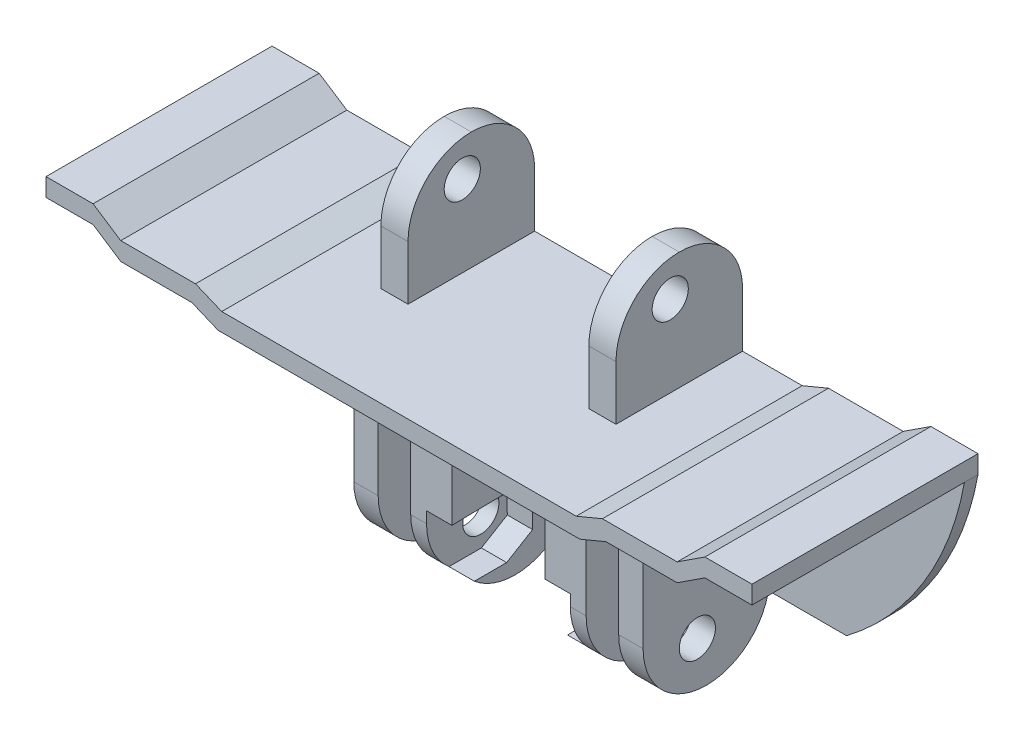
SolidWorks part; units mm, degrees
ref_plane "Front Plane" through (0, 0, 0) normal (0, 0, 1) x (1, 0, 0)
ref_plane "Top Plane" through (0, 0, 0) normal (0, 1, 0) x (1, 0, 0)
ref_plane "Right Plane" through (0, 0, 0) normal (1, 0, 0) x (0, 0, -1)
sketch "Sketch2" plane through (0, 0, 0) normal (0, 0, 1) x (1, 0, 0)
  line L0 (-5, 6) -> (-10, 6)
  line L1 (-5, 6) -> (5, 6) construction
  line L2 (-5, 6) -> (-5, -19) construction
  line L4 (5, 6) -> (5, -19) construction
  line L7 (-10, 6) -> (-10, -19)
  line L8 (-10, -19) -> (-5, -19)
  line L9 (-5, -19) -> (-5, 6)
  line L10 (0, 6) -> (0, -6) construction
  line L11 (10, -19) -> (5, -19)
  line L12 (10, 6) -> (10, -19)
  line L13 (5, 6) -> (10, 6)
  line L14 (5, -19) -> (5, 6)
  point P0 (0, 0)
  point P11 (0, 0)
  point P16 (0, 6)
  dimension "D1" = 25
  dimension "D2" = 10
  dimension "D3" = 5
extrude "Boss-Extrude1" add sketch "Sketch2" along normal blind 14
sketch "Sketch4" plane through (0, 0, 0) normal (0, 0, 1) x (1, 0, 0)
  line L0 (0, 0) -> (0, 50000) construction
  line L1 (-6.1796, 6) -> (49993.8204, 6) construction
  line L2 (-10, 6) -> (-20, 6)
  line L3 (10, 6) -> (20, 6)
  line L4 (-20, 6) -> (-22.9016, 7.2064)
  line L5 (-22.9016, 7.2064) -> (-26, 7.2064)
  line L6 (-10, 8) -> (-19.6008, 8)
  line L7 (-19.6008, 8) -> (-22.5024, 9.2064)
  line L8 (-22.5024, 9.2064) -> (-26, 9.2064)
  line L9 (-26, 9.2064) -> (-26, 7.2064)
  line L10 (-10, 6) -> (10, 6)
  line L11 (-10, 8) -> (10, 8)
  line L12 (10, 8) -> (19.6008, 8)
  line L13 (19.6008, 8) -> (22.5024, 9.2064)
  line L14 (20, 6) -> (22.9016, 7.2064)
  line L15 (22.9016, 7.2064) -> (26, 7.2064)
  line L17 (22.5024, 9.2064) -> (26, 9.2064)
  line L18 (-26, 7.2064) -> (-30.766, 7.2064)
  line L19 (-30.766, 7.2064) -> (-33.8312, 9.2064)
  line L20 (-33.8312, 9.2064) -> (-39.0379, 9.2064)
  line L21 (-39.0379, 9.2064) -> (-39.0379, 11.2064)
  line L22 (-39.0379, 11.2064) -> (-33.8312, 11.2064)
  line L23 (-26, 9.2064) -> (-30.766, 9.2064)
  line L24 (-30.766, 9.2064) -> (-33.8312, 11.2064)
  line L25 (26, 7.2064) -> (30.766, 7.2064)
  line L26 (26, 9.2064) -> (30.766, 9.2064)
  line L27 (30.766, 9.2064) -> (33.8312, 11.2064)
  line L28 (30.766, 7.2064) -> (33.8312, 9.2064)
  line L29 (33.8312, 9.2064) -> (39.0379, 9.2064)
  line L30 (39.0379, 9.2064) -> (39.0379, 11.2064)
  line L31 (39.0379, 11.2064) -> (33.8312, 11.2064)
  line L32 (26, 7.2064) -> (26, 9.2064)
  point P19 (0, 6)
  point P20 (0, 8)
  dimension "D1" = 10
  dimension "D2" = 2
extrude "Boss-Extrude3" add sketch "Sketch4" along normal blind 25 contours L23 L24 L22 L21 L20 L19 L18 L9 | L15 L32 L17 L13 L12 L11 L6 L7 L8 L9 L5 L4 L2 L10 L3 L14 | L32 L25 L28 L29 L30 L31 L27 L26 region at (0, 7.2239, 0) region at (-32.5189, 9.2402, 0) region at (32.5189, 9.2402, 0)
sketch "Sketch9" plane through (0, 0, 14) normal (0, 0, 1) x (1, 0, 0)
  line L0 (-10, -19) -> (-5, -19) construction
  line L1 (-5, 6) -> (-7.5, 6)
  line L2 (-5, 6) -> (-5, -19)
  line L3 (-5, -19) -> (-7.5, -19)
  line L4 (-7.5, 6) -> (-7.5, -19)
  line L5 (0, 7.972) -> (0, -7.972) construction
  line L6 (5, -19) -> (7.5, -19)
  line L7 (7.5, 6) -> (7.5, -19)
  line L8 (5, 6) -> (7.5, 6)
  line L9 (5, 6) -> (5, -19)
  point P11 (0, 0)
  dimension "D1" = 2.5
extrude "Cut-Extrude1" [suppressed] cut sketch "Sketch9" against normal blind 10
sketch "Sketch5" plane through (0, 0, 0) normal (0, 0, 1) x (1, 0, 0)
  line L0 (-10, 4.6) -> (-10, 50004.6) construction
  line L1 (0, 0) -> (0, 50000) construction
  line L2 (-10, 8) -> (-10, 21)
  line L3 (-19.6008, 8) -> (19.6008, 8) construction
  line L4 (-10, 21) -> (-13, 21)
  line L5 (-13, 21) -> (-13, 8)
  line L6 (-13, 8) -> (-10, 8)
  line L7 (13, 8) -> (10, 8)
  line L8 (13, 21) -> (13, 8)
  line L9 (10, 21) -> (13, 21)
  line L10 (10, 8) -> (10, 21)
  dimension "D1" = 3
  dimension "D2" = 13
extrude "Boss-Extrude4" add sketch "Sketch5" along normal blind 14
sketch "Sketch7" plane through (0, 0, 0) normal (0, 0, 1) x (1, 0, 0)
  line L0 (-13, 5.6) -> (-13, -49994.4) construction
  line L1 (-19.6008, 5.6) -> (-19.6008, -49994.4) construction
  line L2 (-10.0004, -19) -> (49989.9996, -19) construction
  line L3 (-15.0004, 6) -> (-50015.0004, 6) construction
  line L4 (-16, 6) -> (-16, -19)
  line L5 (-16, -19) -> (-13, -19)
  line L6 (-13, -19) -> (-13, 6)
  line L7 (-13, 6) -> (-16, 6)
  line L8 (0, 0) -> (0, -50000) construction
  line L13 (0, -13.75) -> (0, 13.75) construction
  line L14 (13, -19) -> (13, 6)
  line L15 (16, -19) -> (13, -19)
  line L16 (16, 6) -> (16, -19)
  line L17 (13, 6) -> (16, 6)
  dimension "D1" = 3
extrude "Boss-Extrude5" add sketch "Sketch7" along normal blind 14
sketch "Sketch15" plane through (0, -19, 0) normal (0, -1, 0) x (1, 0, 0)
  line L16 (-10, 14) -> (-9.7, 14)
  line L17 (-10, 14) -> (-5, 14) construction
  line L18 (-10, 14) -> (-10, 0) construction
  line L19 (-9.7, 14) -> (-9.7, 0)
  line L20 (-10, 0) -> (-5, 0) construction
  line L21 (-9.7, 0) -> (-10, 0)
  line L22 (-10, 0) -> (-10, 14)
  line L23 (0, -13.75) -> (0, 13.75) construction
  line L24 (9.7, 0) -> (10, 0)
  line L25 (9.7, 14) -> (9.7, 0)
  line L26 (10, 14) -> (9.7, 14)
  line L27 (10, 0) -> (10, 14)
  line L28 (-13, 14) -> (-13.3, 14)
  line L29 (-16, 14) -> (-13, 14) construction
  line L30 (-13.3, 14) -> (-13.3, 0)
  line L31 (-16, 0) -> (-13, 0) construction
  line L32 (-13.3, 0) -> (-13, 0)
  line L33 (-13, 0) -> (-13, 14)
  line L34 (13.3, 0) -> (13, 0)
  line L35 (13.3, 14) -> (13.3, 0)
  line L36 (13, 14) -> (13.3, 14)
  line L37 (13, 0) -> (13, 14)
  dimension "D1" = 0.3
  dimension "D2" = 0.3
extrude "Cut-Extrude2" cut sketch "Sketch15" against normal up to surface (25 mm away) up to face at (0, 6, 8.1)
sketch "Sketch16" plane through (0, -19, 0) normal (0, -1, 0) x (1, 0, 0)
  line L0 (-5, 14) -> (-5.15, 14)
  line L1 (-9.7, 14) -> (-5, 14) construction
  line L2 (-5.15, 14) -> (-5.15, 0)
  line L3 (-9.7, 0) -> (-5, 0) construction
  line L4 (-5.15, 0) -> (-5, 0)
  line L5 (-5, 0) -> (-5, 14)
  line L6 (0, -13.75) -> (0, 13.75) construction
  line L7 (5.15, 0) -> (5, 0)
  line L8 (5.15, 14) -> (5.15, 0)
  line L9 (5, 14) -> (5.15, 14)
  line L10 (5, 0) -> (5, 14)
  dimension "D1" = 0.15
extrude "Cut-Extrude3" cut sketch "Sketch16" against normal up to surface (25 mm away) up to face at (0, 6, 8.1)
fillet "Fillet1" radius 7 8 edges at (7.425, -19, 0) (7.425, -19, 14) (-7.425, -19, 0) (-7.425, -19, 14) (-14.65, -19, 0) (-14.65, -19, 14) (14.65, -19, 0) (14.65, -19, 14)
hole_wizard "Ø4.0mm Dowel Hole2" positions "Sketch10" profile "Sketch11" hole size "Ø4.0" standard "ANSI Metric" end condition through all
sketch "Sketch10" plane through (16, 0, 0) normal (1, 0, 0) x (0, 0, -1)
  line L7 (-25, 6) -> (0, 6) construction
  line L9 (-14, -12) -> (-14, 6) construction
  point P0 (-8, -14)
  dimension "D1" = 6
  dimension "D2" = 20
sketch "Sketch11" plane through (16, -14, 8) normal (0, 1, 0) x (0, 0, -1)
  line L0 (0, 0) -> (0, 55.0379)
  line L1 (0, 55.0379) -> (2, 55.0379)
  line L2 (2, 55.0379) -> (2, 0)
  line L5 (2, 0) -> (0, 0)
  line L11 (0, -6.35) -> (0, 107.95) construction
  dimension "Thru Hole Dia." = 4
  dimension "Thru Hole Depth" = 55.0379
fillet "Fillet2" radius 7 4 edges at (-11.5, 21, 0) (-11.5, 21, 14) (11.5, 21, 0) (11.5, 21, 14)
hole_wizard "Ø4.0mm Dowel Hole1" positions "Sketch12" profile "Sketch13" hole size "Ø4.0" standard "ANSI Metric"
sketch "Sketch12" plane through (13, 0, 0) normal (1, 0, 0) x (0, 0, -1)
  line L1 (-25, 8) -> (0, 8) construction
  line L2 (-25, 8) -> (0, 8)
  circle A8 centre (-8, -14) radius 2 construction
  circle A9 centre (-8, -14) radius 2
  point P10 (-8, 17)
  dimension "D1" = 9
sketch "Sketch13" plane through (13, 17, 8) normal (0, 1, 0) x (0, 0, -1)
  line L0 (0, 0) -> (0, 27.2017)
  line L1 (0, 27.2017) -> (2, 26)
  line L2 (2, 26) -> (2, 0)
  line L5 (2, 0) -> (0, 0)
  line L10 (0, 27.2017) -> (-2, 26) construction
  line L11 (0, -6.35) -> (0, 107.95) construction
  dimension "Hole Dia." = 4
  dimension "Hole Depth" = 26
  dimension "Drill Angle" = 118
sketch "Sketch14" plane through (0, 0, 0) normal (0, 0, 1) x (1, 0, 0)
  line L4 (0, 14.6739) -> (0, -14.6739) construction
  line L5 (-26, 7.2064) -> (-22.9016, 7.2064)
  line L6 (-26, 6) -> (-26, 7.2064)
  line L7 (-20, 6) -> (-26, 6)
  line L8 (-22.9016, 7.2064) -> (-20, 6)
  line L13 (-16, 6) -> (-20, 6)
  line L14 (-26, -12) -> (-26, 6)
  line L15 (-16, -12) -> (-26, -12)
  line L18 (-16, 6) -> (-16, -12)
  line L21 (16, 6) -> (16, -12)
  line L22 (16, -12) -> (26, -12)
  line L23 (26, -12) -> (26, 6)
  line L24 (16, 6) -> (20, 6)
  line L25 (22.9016, 7.2064) -> (20, 6)
  line L26 (20, 6) -> (26, 6)
  line L27 (26, 6) -> (26, 7.2064)
  line L28 (26, 7.2064) -> (22.9016, 7.2064)
  line L29 (33.8312, 9.2064) -> (39.0379, 9.2064) construction
  line L30 (30.766, 7.2064) -> (33.8312, 9.2064) construction
  line L31 (22.9016, 7.2064) -> (30.766, 7.2064) construction
  line L32 (33.8312, 9.2064) -> (39.0379, 9.2064)
  line L33 (30.766, 7.2064) -> (33.8312, 9.2064)
  line L34 (22.9016, 7.2064) -> (30.766, 7.2064)
  line L35 (-33.8312, 9.2064) -> (-39.0379, 9.2064) construction
  line L36 (-30.766, 7.2064) -> (-33.8312, 9.2064) construction
  line L37 (-22.9016, 7.2064) -> (-30.766, 7.2064) construction
  line L38 (-33.8312, 9.2064) -> (-39.0379, 9.2064)
  line L39 (-30.766, 7.2064) -> (-33.8312, 9.2064)
  line L40 (-22.9016, 7.2064) -> (-30.766, 7.2064)
  line L41 (-13.3, -12) -> (-16, -12) construction
  arc A0 (-39.0379, 9.2064) -> (-26, -12) centre (-5.4018, 15.2751) ccw
  arc A1 (26, -12) -> (39.0379, 9.2064) centre (5.4018, 15.2751) ccw
  point P11 (0, 0)
extrude "Boss-Extrude6" add sketch "Sketch14" along normal blind 1.5 contours L8 L5 L6 L7 | L14 L13 L7 | L27 L28 L25 L26 | L26 L24 L21 L22 L23 | L38 A0 L14 L6 L40 L39 | L23 A1 L32 L33 L34 L27 region at (-23.6483, 6.5391, 0) region at (-31.1404, 0.7095, 0) region at (-21, -3, 0) region at (21, -3, 0) region at (23.6483, 6.5391, 0) region at (31.1404, 0.7095, 0)
sketch "Sketch18" plane through (-5.15, 0, 0) normal (1, 0, 0) x (0, 0, -1)
  line L10 (-7.9408, -17.3481) -> (-22.2123, -17.3481)
  line L17 (-5.13, -12.2747) -> (-8.0592, -10.6519)
  line L18 (-8.0592, -10.6519) -> (-10.9291, -12.3772)
  line L19 (-10.9291, -12.3772) -> (-10.87, -15.7253)
  line L20 (-10.87, -15.7253) -> (-7.9408, -17.3481)
  line L21 (-7.9408, -17.3481) -> (-5.0709, -15.6228)
  line L22 (-5.0709, -15.6228) -> (-5.13, -12.2747)
  line L23 (-8.0592, -10.6519) -> (-22.2123, -10.902)
  line L24 (-22.2123, -10.902) -> (-22.2123, -17.3481)
  circle A0 centre (-8, -14) radius 2.9 construction
  circle M7 centre (-8, -14) radius 2
  arc M8 (-14, -12) -> (-7, -19) centre (-7, -12) ccw
  line M12 (-14, 6) -> (-14, -12)
  dimension "D1" = 5.8
extrude "Cut-Extrude4" cut sketch "Sketch18" against normal blind 2.8 contours L21 L22 L17 L18 L19 L20 M7 | L23 L24 L10 M8 M12 | L18 L23 L10 L20 L19 M12 M8 region at (-5.15, -13.6598, 11.722) region at (-5.15, -16.4589, 9.3623) region at (-5.15, -14.2277, 17.7524)
mirror "Mirror1" about plane through (0, 0, 0) normal (1, 0, 0) of "Cut-Extrude4"
